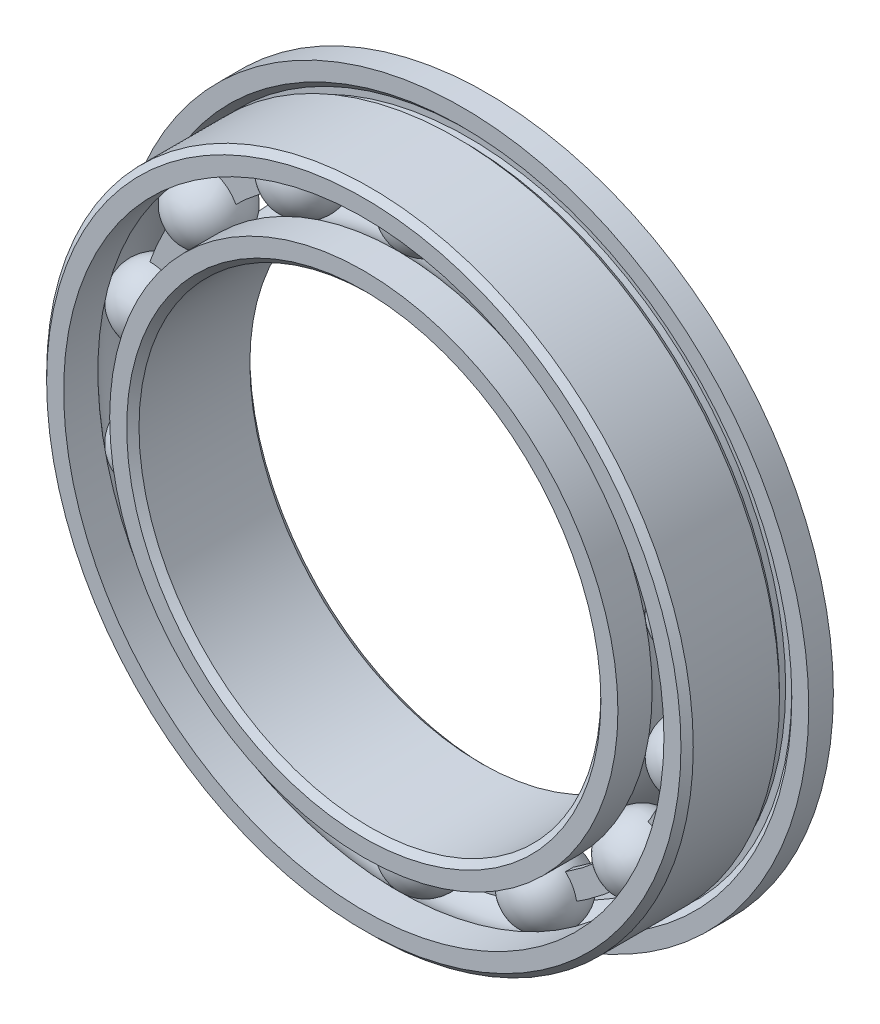
SolidWorks part; units mm, degrees
ref_plane "Front Plane" through (0, 0, 0) normal (0, 0, 1) x (1, 0, 0)
ref_plane "Top Plane" through (0, 0, 0) normal (0, 1, 0) x (1, 0, 0)
ref_plane "Right Plane" through (0, 0, 0) normal (1, 0, 0) x (0, 0, -1)
sketch "Sketch1" plane through (0, 0, 0) normal (1, 0, 0) x (0, 0, -1)
  line L0 (-2, 0) -> (2, 0) construction
  line L1 (0, 10.5) -> (0, -10.5) construction
  line L2 (1.8, 10.5) -> (-1.8, 10.5) construction
  line L3 (-1.8, 10.5) -> (-2, 10.3)
  line L4 (-2, 10.3) -> (-2, 9.7473)
  line L5 (-2, 9.7473) -> (-0.8889, 9.7473)
  line L6 (2, 9.7473) -> (0.8889, 9.7473)
  line L7 (2, 10.3) -> (2, 9.7473)
  line L8 (1.8, 10.5) -> (2, 10.3) construction
  line L9 (0, 10.5) -> (0, 9) construction
  line L10 (0, 9) -> (0, 7.5) construction
  line L11 (1.2, 0) -> (1.2, 10.5) construction
  line L12 (2, 10.3) -> (2, 11.25)
  line L13 (2, 11.25) -> (1.2, 11.25)
  line L14 (1.2, 11.25) -> (1.2, 10.7)
  line L15 (1.2, 10.7) -> (1.4, 10.5)
  line L16 (1.4, 10.5) -> (1.4, 10.3)
  line L17 (1.4, 10.3) -> (1.2, 10.3)
  line L18 (1.2, 10.3) -> (1, 10.5)
  line L19 (-1.8, 10.5) -> (1, 10.5)
  line L20 (2, 11.25) -> (2, -11.25) construction
  line L21 (1.2, 10.5) -> (1.2, 10.7) construction
  line L22 (1.2, 10.5) -> (1, 10.5) construction
  arc A0 (-0.8889, 9.7473) -> (0.8889, 9.7473) centre (0, 9) cw
  point P14 (0, 7.5)
  point P15 (1.2, 0)
  point P25 (2, 0)
  dimension "Width" = 4
  dimension "OD" = 21
  dimension "D1" = 45
  dimension "D2" = 0.2
  dimension "ID" = 15
  dimension "D3" = 1.7778
  dimension "D4" = 0.7473
  dimension "Th" = 0.8
  dimension "Flange OD" = 22.5
revolve "Revolve1" add sketch "Sketch1" angle 360 about L0
sketch "Sketch3" plane through (0, 0, 0) normal (1, 0, 0) x (0, 0, -1)
  line L0 (-2, 8.2527) -> (-0.8889, 8.2527)
  line L1 (0, 10.5) -> (0, -10.5) construction
  line L2 (-2, 10.3) -> (-2, 9.7473) construction
  line L3 (-2, 8.2527) -> (-2, 7.7)
  line L4 (-1.8, 10.5) -> (-2, 10.3) construction
  line L5 (-2, 7.7) -> (-1.8, 7.5)
  line L6 (-1.8, 7.5) -> (1.8, 7.5)
  line L8 (1.8, 7.5) -> (2, 7.7)
  line L10 (2, 7.7) -> (2, 8.2527)
  line L11 (2, 8.2527) -> (0.8889, 8.2527)
  line L13 (1.8, 10.5) -> (2, 10.3) construction
  arc A0 (0.8889, 9.7473) -> (-0.8889, 9.7473) centre (0, 9) ccw construction
  arc A1 (0.8889, 8.2527) -> (-0.8889, 8.2527) centre (0, 9) cw
revolve "Revolve3" add sketch "Sketch3" angle 360 about L0
sketch "Sketch6" plane through (0, 0, 0) normal (1, 0, 0) x (0, 0, -1)
  line L1 (-0.1245, 9.3736) -> (0.1245, 9.3736)
  line L2 (-0.1245, 9.3736) -> (-0.1245, 8.6264)
  line L3 (-0.1245, 8.6264) -> (0.1245, 8.6264)
  line L4 (0.1245, 9.3736) -> (0.1245, 8.6264)
  line L5 (-0.1245, 9.3736) -> (0.1245, 8.6264) construction
  line L6 (-0.1245, 8.6264) -> (0.1245, 9.3736) construction
  point P4 (0, 9)
  dimension "D1" = 0.7473
  dimension "D2" = 0.2491
revolve "Revolve6" add sketch "Sketch6" angle 360 about L0
sketch "Sketch4" plane through (0, 0, 0) normal (1, 0, 0) x (0, 0, -1)
  line L0 (-1.1613, 9) -> (1.1613, 9)
  arc A2 (-1.1613, 9) -> (1.1613, 9) centre (0, 9) cw
  arc A3 (0.8889, 9.7473) -> (-0.8889, 9.7473) centre (0, 9) ccw construction
revolve "Revolve4" add sketch "Sketch4" angle 360 about L0
ref_axis "Axis1" through (0, 0, -2) along (0, 0, 1)
pattern_circular "CirPattern1" count 14 every 25.714 about axis through (0, 0, -2) along (0, 0, 1) of bodies 104
sketch "Sketch5" plane through (0, 0, 0) normal (1, 0, 0) x (0, 0, -1)
  line L0 (-2, 9.7473) -> (-0.8889, 9.7473) construction
  line L1 (-1.9, 9.7473) -> (-1.1613, 9.7473)
  line L2 (-1.9, 9.7473) -> (-1.9, 8.2527)
  line L3 (-1.9, 8.2527) -> (-1.1613, 8.2527)
  line L4 (-1.1613, 9.7473) -> (-1.1613, 8.2527)
  line L5 (-2, 8.2527) -> (-0.8889, 8.2527) construction
  line L6 (2, 9.7473) -> (0.8889, 9.7473) construction
  line L7 (1.9, 9.7473) -> (1.1613, 9.7473)
  line L8 (1.9, 9.7473) -> (1.9, 8.2527)
  line L9 (1.9, 8.2527) -> (1.1613, 8.2527)
  line L10 (1.1613, 9.7473) -> (1.1613, 8.2527)
  line L11 (2, 8.2527) -> (0.8889, 8.2527) construction
  line L12 (-1.8, 10.5) -> (-2, 10.3) construction
  point P18 (-1.9, 10.4)
revolve "Revolve5" [suppressed] add sketch "Sketch5" angle 360 about L0
ref_axis "Center Axis 1" through (0, 0, -1.8) along (0, 0, 1)
ref_plane "Contact Plane 1" through (0, 0, -2) normal (0, 0, -1) x (-1, 0, 0)
ref_plane "Contact Plane 2" through (0, 0, -1.2) normal (0, 0, 1) x (1, 0, 0)
equation "\"D2@Sketch1\" = \"Width@Sketch1\"*.05"
equation "\"D3@Sketch1\" = \"Width@Sketch1\"/2.25"
equation "\"D4@Sketch1\" = (((\"OD@Sketch1\"-\"Width@Sketch1\")/2)/3.25)/3.5"
equation "\"D2@CirPattern1\" = 360/\"Balls@CirPattern1\""
equation "\"D1@Sketch6\"=\"D4@Sketch1\""
equation "\"D2@Sketch6\"=\"D1@Sketch6\"/3"
